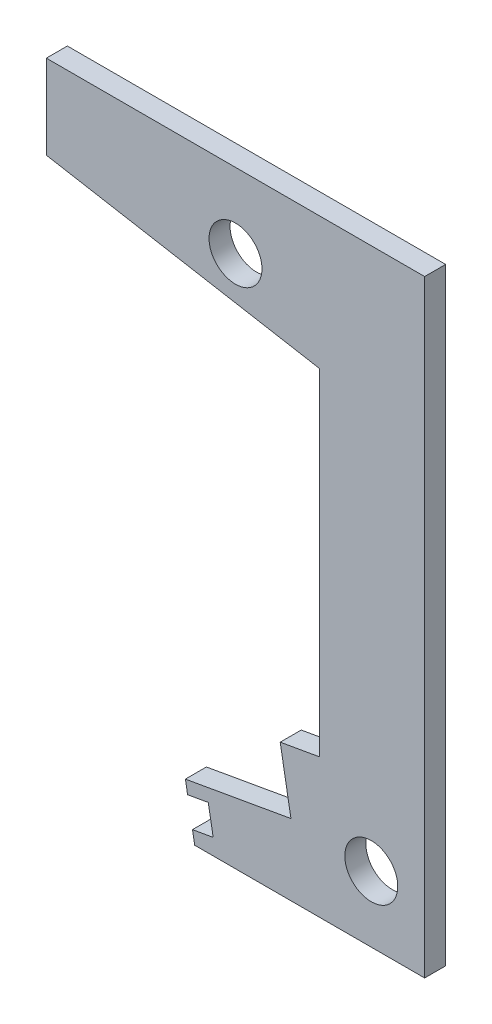
SolidWorks part; units mm, degrees
material "Balsa"
ref_plane "Plan de face" through (0, 0, 0) normal (0, 0, 1) x (1, 0, 0)
ref_plane "Plan de dessus" through (0, 0, 0) normal (0, 1, 0) x (1, 0, 0)
ref_plane "Plan de droite" through (0, 0, 0) normal (1, 0, 0) x (0, 0, -1)
sketch "Esquisse1" plane through (0, 0, 0) normal (0, 0, 1) x (1, 0, 0)
  line L0 (-65, 51.4613) -> (0, 40)
  line L1 (0, 40) -> (0, -40)
  line L2 (-6.8091, -56.1122) -> (-9.3591, -41.6503)
  line L3 (-9.3591, -41.6503) -> (0, -40)
  line L4 (-6.8091, -56.1122) -> (-31.9182, -60.5396)
  line L5 (-29.71, -73.063) -> (25, -73.063)
  line L6 (25, -73.063) -> (25, 71.4613)
  line L7 (25, 71.4613) -> (-65, 71.4613)
  line L8 (-65, 71.4613) -> (-65, 51.4613)
  line L9 (7.1417, -5.2313) -> (92.0944, -5.2313) construction
  line L10 (-31.9182, -60.5396) -> (-29.71, -73.063)
  circle A0 centre (-20, 53.6808) radius 6.3
  circle A1 centre (12.3113, -57.3983) radius 6.3
  dimension "D1" = 12.6
  dimension "D2" = 10
  dimension "D3" = 20
  dimension "D4" = 80
  dimension "D5" = 65
  dimension "D6" = 100
  dimension "D7" = 100
  dimension "D8" = 20
  dimension "D9" = 35
  dimension "D10" = 90
  dimension "D11" = 9.5035
  dimension "D12" = 14.685
extrude "Boss.-Extru.1" add sketch "Esquisse1" along normal blind 5
sketch "Esquisse2" plane through (0, 0, 0) normal (0, 0, -1) x (-1, 0, 0)
  line L0 (31.3966, -63.498) -> (30.231, -70.1086)
  line L1 (31.3966, -63.498) -> (26.4726, -62.6297)
  line L2 (30.231, -70.1086) -> (25.3069, -69.2404)
  line L3 (26.4726, -62.6297) -> (25.3069, -69.2404)
  line L11 (31.9182, -60.5396) -> (29.71, -73.063) construction
  line L12 (6.8091, -56.1122) -> (31.9182, -60.5396) construction
  dimension "D2" = 5
  dimension "D3" = 3.004
  dimension "D4" = 3
extrude "Enlèv. mat.-Extru.1" cut sketch "Esquisse2" against normal blind 5
